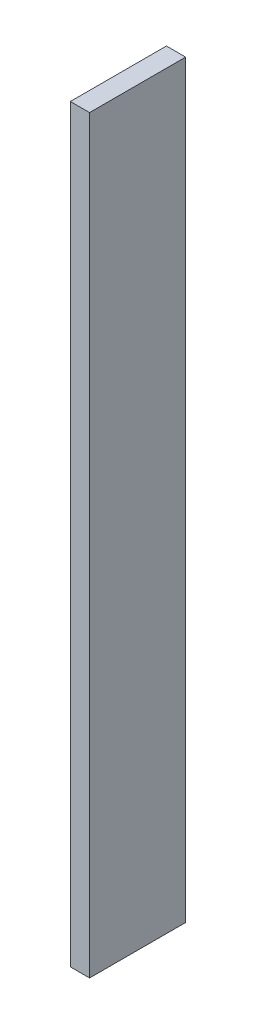
SolidWorks part; units mm, degrees
ref_plane "Plan de face" through (0, 0, 0) normal (0, 0, 1) x (1, 0, 0)
ref_plane "Plan de dessus" through (0, 0, 0) normal (0, 1, 0) x (1, 0, 0)
ref_plane "Plan de droite" through (0, 0, 0) normal (1, 0, 0) x (0, 0, -1)
sketch "Esquisse1" plane through (0, 0, 0) normal (1, 0, 0) x (0, 0, -1)
  line L1 (-25, -195) -> (25, -195)
  line L2 (-25, -195) -> (-25, 195)
  line L3 (-25, 195) -> (25, 195)
  line L4 (25, -195) -> (25, 195)
  line L5 (-25, -195) -> (25, 195) construction
  line L6 (-25, 195) -> (25, -195) construction
  point P0 (0, 0)
  dimension "D1" = 50
  dimension "D2" = 390
extrude "Boss.-Extru.1" add sketch "Esquisse1" along normal blind 10
